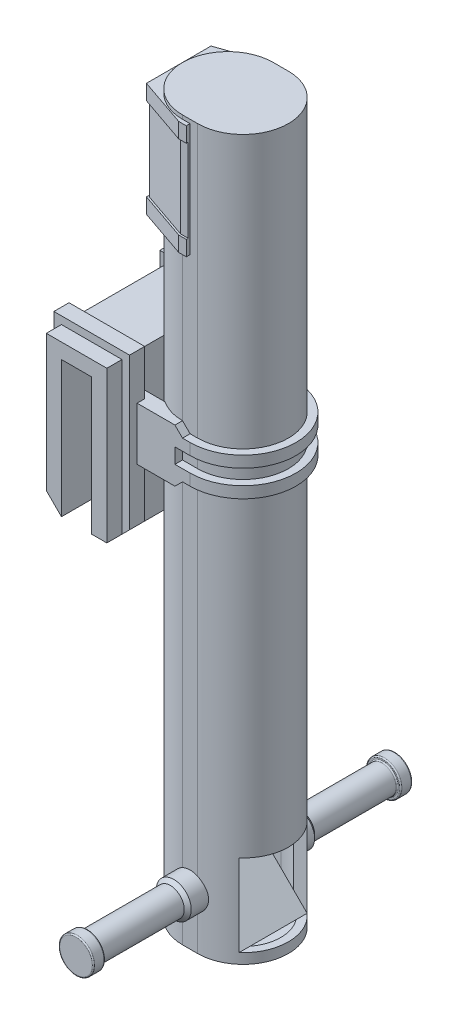
SolidWorks part; units mm, degrees
ref_plane "Front Plane" through (0, 0, 0) normal (0, 0, 1) x (1, 0, 0)
ref_plane "Top Plane" through (0, 0, 0) normal (0, 1, 0) x (1, 0, 0)
ref_plane "Right Plane" through (0, 0, 0) normal (1, 0, 0) x (0, 0, -1)
sketch "Sketch1" plane through (0, 0, 0) normal (0, 0, 1) x (1, 0, 0)
  line L0 (-51.9447, -77.5874) -> (-61.9447, -67.5874)
  line L1 (-51.9447, 12.4126) -> (-31.9447, 12.4126)
  line L2 (-51.9447, 12.4126) -> (-51.9447, -77.5874)
  line L4 (-31.9447, 12.4126) -> (-31.9447, -77.5874)
  line L5 (-61.9447, -67.5874) -> (-61.9447, 22.4126)
  line L6 (-61.9447, 22.4126) -> (-21.9447, 22.4126)
  line L7 (-21.9447, 22.4126) -> (-21.9447, -77.5874)
  line L8 (-21.9447, -77.5874) -> (-31.9447, -77.5874)
  line L9 (-21.9447, 9.0563) -> (-31.9447, 9.0563) construction
  line L10 (-42.9825, 22.4126) -> (-42.9825, 12.4126) construction
  line L11 (-61.9447, 9.0563) -> (-51.9447, 9.0563) construction
  dimension "D1" = 40
  dimension "D2" = 90
  dimension "D3" = 45
  dimension "D4" = 10
extrude "Boss-Extrude1" add sketch "Sketch1" along normal blind 100
sketch "Sketch3" plane through (0, 0, 100) normal (0, 0, 1) x (1, 0, 0)
  line L0 (-61.9447, -67.5874) -> (-66.9447, -67.5874)
  line L1 (-41.2735, 22.4126) -> (-41.2735, 27.4126)
  line L2 (-21.9447, 22.4126) -> (-61.9447, 22.4126) construction
  line L3 (-21.9447, -33.0039) -> (-16.9447, -33.0039)
  line L4 (-21.9447, -77.5874) -> (-21.9447, 22.4126) construction
  line L5 (-66.9447, -67.5874) -> (-66.9447, 27.4126)
  line L6 (-66.9447, 27.4126) -> (-16.9447, 27.4126)
  line L7 (-16.9447, 27.4126) -> (-16.9447, -72.5874)
  line L8 (-16.9447, -72.5874) -> (-21.9447, -77.5874)
  line L9 (-21.9447, -77.5874) -> (-21.9447, 22.4126)
  line L10 (-21.9447, 22.4126) -> (-61.9447, 22.4126)
  line L11 (-61.9447, 22.4126) -> (-61.9447, -67.5874)
  line M8 (-21.9447, -77.5874) -> (-21.9447, 22.4126)
  line M9 (-21.9447, 22.4126) -> (-61.9447, 22.4126)
  line M10 (-61.9447, 22.4126) -> (-61.9447, -67.5874)
  dimension "D1" = 5
extrude "Boss-Extrude2" add sketch "Sketch3" against normal blind 10 from offset 10 contours L6 L5 L0 L1 M10 M9 | L7 L6 L1 L3 M9 M8 | L8 L7 L3 M8 region at (-62.1509, -12.0456, 100) region at (-40.6222, 24.9126, 100) region at (-19.4942, -54.0704, 100) offset against normal yes
ref_plane "Plane1" through (0, 0, 50) normal (0, 0, -1) x (-1, 0, 0)
mirror "Mirror1" about plane through (0, 0, 50) normal (0, 0, -1) of "Boss-Extrude2"
sketch "Sketch4" plane through (-21.9447, 0, 0) normal (1, 0, 0) x (0, 0, -1)
  line L0 (-85, 30.3631) -> (-85, -69.6369) construction
  line L1 (-50, -22) -> (-50, 22) construction
  line L2 (-15, -37.5874) -> (-25, -37.5874)
  line L3 (-77.6412, -2.5874) -> (-77.6412, 22.4126) construction
  line L4 (-25, -2.5874) -> (-25, -37.5874)
  line L5 (-15, -72.5874) -> (-15, 27.4126) construction
  line L6 (-15, -2.5874) -> (-25, -2.5874)
  line L7 (-85, -2.5874) -> (-75, -2.5874)
  line L8 (-85, -2.5874) -> (-85, -37.5874)
  line L9 (-85, -37.5874) -> (-75, -37.5874)
  line L10 (-75, -2.5874) -> (-75, -37.5874)
  line L11 (-80, 22.4126) -> (-20, 22.4126) construction
  line L12 (-15, -2.5874) -> (-15, -37.5874)
  dimension "D1" = 25
  dimension "D2" = 35
  dimension "D3" = 10
  dimension "D4" = 25
extrude "Boss-Extrude3" add sketch "Sketch4" along normal blind 30
sketch "Sketch7" plane through (0, -2.5874, 0) normal (0, 1, 0) x (1, 0, 0)
  line L1 (8.0553, -15) -> (8.0553, -25) construction
  line L2 (8.0553, -75) -> (8.0553, -85) construction
  line L3 (8.0553, -20) -> (18.0553, -20)
  line L4 (8.0553, -80) -> (18.0553, -80)
  line L5 (-21.9447, -40.6008) -> (-21.9447, -59.3992)
  line L6 (-21.9447, -59.3992) -> (-20.4342, -59.3992)
  line L8 (-21.9447, -40.6008) -> (-20.4342, -40.6008)
  line L9 (-20.4342, -59.3992) -> (-20.4342, -40.6008)
  arc A0 (8.0553, -20) -> (8.0553, -80) centre (8.0553, -50) ccw
  arc A1 (18.0553, -80) -> (18.0553, -20) centre (18.0553, -50) ccw
  point P11 (-21.9447, -50)
  line M4 (8.0553, -85) -> (8.0553, -75)
  line M5 (8.0553, -75) -> (-21.9447, -75)
extrude "Boss-Extrude6" add sketch "Sketch7" along normal up to surface and the other way up to surface contours A0 L5 L6 | A0 L8 L5 | A0 L9 region at (-21.4936, -2.5874, 42.9386) region at (-21.0397, -2.5874, 50) region at (-21.4936, -2.5874, 57.0614) up to face at (-41.9447, 22.4126, 50) other way up to face at (-24.4447, -77.5874, 50)
extrude "Boss-Extrude7" add sketch "Sketch7<3>" along normal blind 175 and the other way blind 300 contours L4 A1 L3 A0 L9 M5 M4 | A0 M5 M4 | A0 L9 region at (13.4384, -2.5874, 49.5465) region at (-21.0397, -2.5874, 50) region at (1.7612, -2.5874, 77.015)
sketch "Sketch7<3>" plane through (0, -2.5874, 0) normal (0, 1, 0) x (1, 0, 0) same geometry as "Sketch7"
sketch "Sketch8" plane through (0, -2.5874, 0) normal (0, 1, 0) x (1, 0, 0)
  line L0 (18.0553, -85) -> (18.0553, -15) construction
  line L1 (18.0553, -85) -> (8.0553, -85)
  line L2 (8.0553, -85) -> (8.0553, -80)
  line L3 (8.0553, -80) -> (18.0553, -80)
  line L4 (18.0553, -15) -> (8.0553, -15)
  line L5 (8.0553, -15) -> (8.0553, -20)
  line L6 (8.0553, -20) -> (18.0553, -20)
  arc A0 (18.0553, -85) -> (18.0553, -15) centre (18.0553, -50) ccw
  arc A1 (18.0553, -80) -> (18.0553, -20) centre (18.0553, -50) ccw
extrude "Boss-Extrude8" add sketch "Sketch8" against normal blind 25 from offset 5 offset against normal yes
chamfer "Chamfer2" distance 5 angle 45 4 edges at (8.0553, -7.5874, 17.5) (8.0553, -32.5874, 17.5) (8.0553, -32.5874, 82.5) (8.0553, -7.5874, 82.5)
extrude "Cut-Extrude1" cut sketch "Sketch8<2>" against normal mid plane 10 from offset 17.5 offset against normal yes
sketch "Sketch8<2>" plane through (0, -2.5874, 0) normal (0, 1, 0) x (1, 0, 0) same geometry as "Sketch8"
sketch "Sketch9" plane through (0, 172.4126, 0) normal (0, 1, 0) x (1, 0, 0)
  line L0 (8.0553, -20) -> (-21.9447, -30.3004)
  line L1 (-21.9447, -40.6008) -> (-21.9447, -20) construction
  line L2 (-21.9447, -30.3004) -> (-21.9447, -69.6996)
  line L3 (-21.9447, -80) -> (-21.9447, -59.3992) construction
  line L4 (-21.9447, -69.6996) -> (8.0553, -80)
  line L5 (8.0553, -80) -> (8.0553, -20)
  line L6 (8.0553, -50) -> (-21.9447, -50) construction
  line L7 (-21.9447, -40.6008) -> (-20.4342, -40.6008)
  line L8 (8.0553, -15) -> (8.0553, -20) construction
  line L9 (-21.9447, -59.3992) -> (-20.4342, -59.3992)
  line L10 (8.0553, -80) -> (8.0553, -85) construction
  line L11 (-21.9447, -69.6996) -> (-21.9447, -72.1996)
  line L12 (-21.9447, -30.3004) -> (-21.9447, -27.8004)
  line L14 (-24.4447, -28.6588) -> (-24.4447, -71.3412)
  line L15 (8.0553, -17.5) -> (-24.4447, -28.6588)
  line L16 (8.0553, -82.5) -> (-24.4447, -71.3412)
  line L17 (8.0553, -82.5) -> (13.0553, -82.5)
  line L18 (13.0553, -80) -> (13.0553, -85) construction
  line L19 (13.0553, -82.5) -> (13.0553, -80)
  line L20 (8.0553, -80) -> (18.0553, -80) construction
  line L21 (13.0553, -80) -> (8.0553, -80)
  line L22 (8.0553, -20) -> (13.0553, -20)
  line L23 (8.0553, -20) -> (18.0553, -20) construction
  line L24 (13.0553, -20) -> (13.0553, -17.5)
  line L25 (13.0553, -15) -> (13.0553, -20) construction
  line L26 (13.0553, -17.5) -> (8.0553, -17.5)
  arc A1 (-20.4342, -40.6008) -> (-20.4342, -59.3992) centre (8.0553, -50) ccw
  arc M12 (8.0553, -20) -> (8.0553, -80) centre (8.0553, -50) ccw
  line M13 (8.0553, -80) -> (18.0553, -80)
  line M15 (18.0553, -20) -> (8.0553, -20)
extrude "Boss-Extrude11" add sketch "Sketch9" against normal blind 75 from offset 2.5 contours L16 L11 L2 L12 L15 L14 | L7 L2 M12 | L2 L9 M12 | L24 L26 L15 L12 L0 M12 M15 | L17 L19 L4 L11 L16 M13 M12 | L4 M12 | L2 L7 L0 M12 | L9 L2 L4 M12 region at (-1.8078, 172.4126, 21.2734) region at (-18.6106, 172.4126, 32.8725) region at (-1.3705, 172.4126, 77.4529) region at (10.5553, 172.4126, 80.3727) region at (-23.1864, 172.4126, 50) region at (-21.4936, 172.4126, 42.9386) region at (-18.6106, 172.4126, 67.1275) region at (-21.4936, 172.4126, 57.0614) offset against normal yes
ref_plane "Plane2" through (0, 132.4126, 0) normal (0, 1, 0) x (1, 0, 0)
extrude "Cut-Extrude3" cut sketch "Sketch9<4>" against normal mid plane 55 from surface contours L24 L26 L15 L12 L0 M12 M15 | L16 L11 L2 L12 L15 L14 | L2 L7 L0 M12 | L2 L9 M12 | L7 L2 M12 | L9 L2 L4 M12 | L17 L19 L4 L11 L16 M13 M12 | L0 M12 | L4 M12 region at (-1.8078, 172.4126, 21.2734) region at (-1.3705, 172.4126, 22.5471) region at (-18.6106, 172.4126, 32.8725) region at (-1.3705, 172.4126, 77.4529) region at (10.5553, 172.4126, 80.3727) region at (-23.1864, 172.4126, 50) region at (-21.4936, 172.4126, 42.9386) region at (-18.6106, 172.4126, 67.1275) region at (-21.4936, 172.4126, 57.0614) starting at plane "Plane2"
sketch "Sketch9<4>" plane through (0, 172.4126, 0) normal (0, 1, 0) x (1, 0, 0) same geometry as "Sketch9"
sketch "Sketch10" plane through (0, 104.9126, 0) normal (0, 1, 0) x (1, 0, 0)
  line L0 (8.0553, -17.5) -> (8.0553, -20)
  line L1 (8.0553, -15) -> (8.0553, -20) construction
  line L2 (-24.4447, -33.0369) -> (-23.1947, -33.0369)
  line L3 (-24.4447, -28.6588) -> (-24.4447, -71.3412) construction
  line L4 (8.0553, -80) -> (8.0553, -82.5)
  line L5 (8.0553, -81.25) -> (13.0553, -81.25)
  line L6 (13.0553, -82.5) -> (13.0553, -80) construction
  line L7 (13.0553, -81.25) -> (13.0553, -18.75)
  line L8 (13.0553, -20) -> (13.0553, -17.5) construction
  line L9 (13.0553, -18.75) -> (8.0553, -18.75)
  line L10 (8.0553, -18.75) -> (-23.1947, -29.4796)
  line L11 (-23.1947, -29.4796) -> (-23.1947, -70.5204)
  line L12 (-23.1947, -70.5204) -> (8.0553, -81.25)
  line L13 (8.0553, -82.5) -> (-24.4447, -71.3412) construction
  line L14 (8.0553, -17.5) -> (-24.4447, -28.6588) construction
  line M5 (13.0553, -82.5) -> (13.0553, -80)
  line M6 (13.0553, -80) -> (8.0553, -80)
  line M7 (8.0553, -80) -> (-10.373, -73.6727)
  arc M8 (-10.373, -73.6727) -> (-10.373, -26.3273) centre (8.0553, -50) cw
  line M9 (-10.373, -26.3273) -> (8.0553, -20)
  line M10 (8.0553, -20) -> (13.0553, -20)
  line M11 (13.0553, -20) -> (13.0553, -17.5)
extrude "Boss-Extrude12" add sketch "Sketch10" along normal up to surface (55 mm away) contours L11 L12 L4 L0 L10 M7 M8 M9 | L7 M6 M10 M9 M8 M7 | L9 L0 M11 M10 | L4 L5 M5 M6 region at (10.5553, 104.9126, 19.375) region at (7.3566, 104.9126, 19.375) region at (-2.0268, 104.9126, 50) region at (10.5553, 104.9126, 80.625)
sketch "Sketch11" plane through (0, 172.4126, 0) normal (0, 1, 0) x (1, 0, 0)
  line L0 (8.0553, -25) -> (18.0553, -25)
  line L1 (18.0553, -75) -> (8.0553, -75)
  line L2 (18.0553, -80) -> (18.0553, -20) construction
  line L4 (18.0553, -80) -> (13.0553, -80) construction
  line L6 (8.0553, -20) -> (18.0553, -20) construction
  line L7 (8.0553, -80) -> (8.0553, -20) construction
  line L8 (12.3298, -25) -> (12.3298, -20) construction
  arc A0 (18.0553, -75) -> (18.0553, -25) centre (18.0553, -50) ccw
  arc A1 (8.0553, -25) -> (8.0553, -75) centre (8.0553, -50) ccw
  arc A2 (18.0553, -80) -> (18.0553, -20) centre (18.0553, -50) ccw construction
  arc A3 (18.0553, -80) -> (18.0553, -20) centre (18.0553, -50) ccw construction
  point P15 (18.0553, -50)
extrude "Cut-Extrude4" cut sketch "Sketch11" against normal blind 465 from offset 5 contours A1 L1 A0 L0 offset against normal yes
sketch "Sketch13" plane through (-21.9447, 0, 0) normal (1, 0, 0) x (0, 0, -1)
  line L0 (-50, -302.5874) -> (-50, -234.9479)
  line L1 (-80, -302.5874) -> (-20, -302.5874) construction
  line L3 (-72.5, -241.6785) -> (-27.5, -241.6785)
  line L4 (-72.5, -241.6785) -> (-72.5, -295.8568)
  line L5 (-72.5, -295.8568) -> (-27.5, -295.8568)
  line L6 (-27.5, -241.6785) -> (-27.5, -295.8568)
  line L7 (-72.5, -241.6785) -> (-27.5, -295.8568) construction
  line L8 (-72.5, -295.8568) -> (-27.5, -241.6785) construction
  point P4 (-50, -268.7676)
extrude "Cut-Extrude6" cut sketch "Sketch13" against normal blind 39 from offset 80 contours L4 L5 L0 L3 | L6 L3 L0 L5 region at (-21.9447, -268.7676, 61.25) region at (-21.9447, -268.7676, 38.75)
sketch "Sketch15" plane through (0, 0, 27.5) normal (0, 0, 1) x (1, 0, 0)
  line L0 (37.8985, -295.8568) -> (-16.9447, -241.0137)
  line L1 (-16.9447, 167.4126) -> (-16.9447, -297.5874) construction
  line L2 (-16.9447, -241.0137) -> (-16.9447, -246.8949)
  line L3 (-16.9447, -246.8949) -> (32.0172, -295.8568)
  line L4 (28.9526, -295.8568) -> (37.8985, -295.8568) construction
  line L5 (32.0172, -295.8568) -> (37.8985, -295.8568)
extrude "Boss-Extrude13" add sketch "Sketch15" along normal up to surface (45 mm away) contours L0 L2 L3 L5 up to face at (33.4255, -268.7676, 72.5)
sketch "Sketch16" plane through (0, -302.5874, 0) normal (0, -1, 0) x (1, 0, 0)
  line L0 (-16.9447, 72.5) -> (-16.9447, 66.5831)
  line L1 (-16.9447, 72.5) -> (-11.7878, 72.5)
  line L2 (-16.9447, 72.5) -> (-11.7878, 72.5) construction
  line L3 (-16.9447, 27.5) -> (-16.9447, 33.4169)
  line L4 (-16.9447, 27.5) -> (-11.7878, 27.5)
  arc A0 (-11.7878, 72.5) -> (-16.9447, 66.5831) centre (8.0553, 50) ccw
  arc A1 (-16.9447, 33.4169) -> (-11.7878, 27.5) centre (8.0553, 50) ccw
extrude "Cut-Extrude7" cut sketch "Sketch16" against normal blind 72
scale "Scale1" scale about centroid uniform scaling yes scale factor 1.3
sketch "Sketch17" plane through (0, 0, 11) normal (0, 0, -1) x (-1, 0, 0)
  line L2 (-25.1233, -379.9733) -> (-25.1233, -28.9733) construction
  line L3 (-25.1233, -336.0076) -> (-12.1233, -336.0076)
  line L4 (-12.1233, -379.9733) -> (-12.1233, -35.4733) construction
  circle A0 centre (-18.6233, -336.0076) radius 15
  line M1 (-12.1233, -379.9733) -> (-12.1233, -35.4733)
  line M4 (-25.1233, -28.9733) -> (-25.1233, -379.9733)
extrude "Boss-Extrude14" add sketch "Sketch17" along normal blind 100 and the other way blind 0.0001 from offset 2 contours A0 L3 M4 M1 | A0 M4 | A0 L3 M1 M4 | A0 M1 region at (18.6233, -328.7428, 11) region at (28.6224, -336.0076, 11) region at (18.6233, -343.2724, 11) region at (8.6243, -336.0076, 11) offset against normal yes
sketch "Sketch19" plane through (0, 0, -87) normal (0, 0, -1) x (-1, 0, 0)
  circle A0 centre (-18.6233, -336.0076) radius 15
  circle A1 centre (-18.6233, -336.0076) radius 12
extrude "Cut-Extrude8" cut sketch "Sketch19" against normal blind 70 from offset 10 offset against normal yes
chamfer "Chamfer3" distance 4 angle 45 1 edges at (3.6233, -336.0076, -7)
fillet "Fillet1" radius 1 3 edges at (3.6233, -336.0076, -87) (3.6233, -336.0076, -77) (6.6233, -336.0076, -77)
ref_plane "Plane3" through (0, 0, 50) normal (0, 0, -1) x (-1, 0, 0)
mirror "Mirror9" about plane through (0, 0, 50) normal (0, 0, -1) of "Fillet1", "Chamfer3", "Cut-Extrude8", "Boss-Extrude14"
